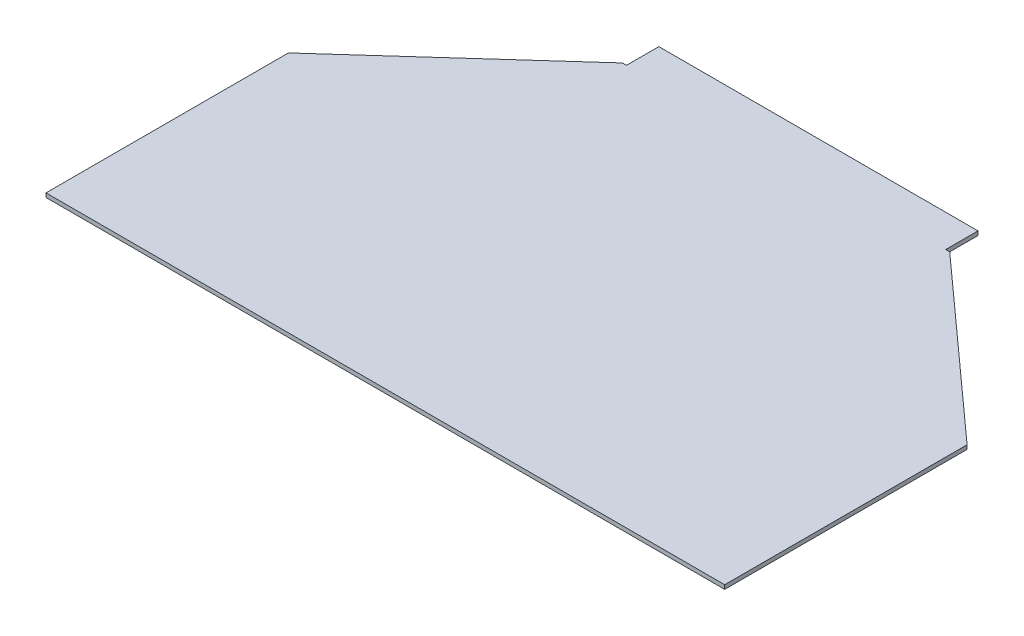
SolidWorks part; units mm, degrees
material "Acrylic (Medium-high impact)"
ref_plane "Front Plane" through (0, 0, 0) normal (0, 0, 1) x (1, 0, 0)
ref_plane "Top Plane" through (0, 0, 0) normal (0, 1, 0) x (1, 0, 0)
ref_plane "Right Plane" through (0, 0, 0) normal (1, 0, 0) x (0, 0, -1)
sketch "Sketch1" plane through (0, 0, 0) normal (0, 1, 0) x (1, 0, 0)
  line L0 (125.4125, 0) -> (-125.4125, 0)
  line L1 (-125.4125, 0) -> (-125.4125, -25.4)
  line L2 (-125.4125, -25.4) -> (-128.5875, -25.4)
  line L3 (-128.5875, -25.4) -> (-266.7, -149.86)
  line L4 (-266.7, -149.86) -> (-266.7, -340.36)
  line L5 (-266.7, -340.36) -> (266.7, -340.36)
  line L6 (266.7, -340.36) -> (266.7, -149.86)
  line L7 (266.7, -149.86) -> (128.5875, -25.4)
  line L8 (128.5875, -25.4) -> (125.4125, -25.4)
  line L9 (125.4125, -25.4) -> (125.4125, 0)
  point P4 (0, 0)
  dimension "D1" = 257.175
  dimension "D2" = 3.175
  dimension "D3" = 340.36
  dimension "D4" = 25.4
  dimension "D5" = 190.5
  dimension "D6" = 533.4
base flange "Base-Flange1" sketch "Sketch1" thickness 3.175 reverse thickness direction no parameters "D1"=0.7366
sketch "Bend-Lines1" [suppressed] plane through (0, 0, 0) normal (0, 1, 0) x (1, 0, 0)
sketch "Bounding-Box1" [suppressed] plane through (0, 0, 0) normal (0, 1, 0) x (1, 0, 0)
sheet metal parameters "Sheet-Metal1" thickness 3.175 parameters "D1"=0.7366
flat pattern "Flat-Pattern1" [suppressed]
sketch "Bend-Lines2" plane through (0, 0, 0) normal (0, 1, 0) x (1, 0, 0)
sketch3d "Bounding-Box2" [suppressed]
  line L0 (-266.7, -340.36, 0) -> (266.7, -340.36, 0) construction
  line L1 (-266.7, 0, 0) -> (266.7, 0, 0) construction
  line L2 (-266.7, -340.36, 0) -> (-266.7, 0, 0) construction
  line L3 (266.7, -340.36, 0) -> (266.7, 0, 0) construction
